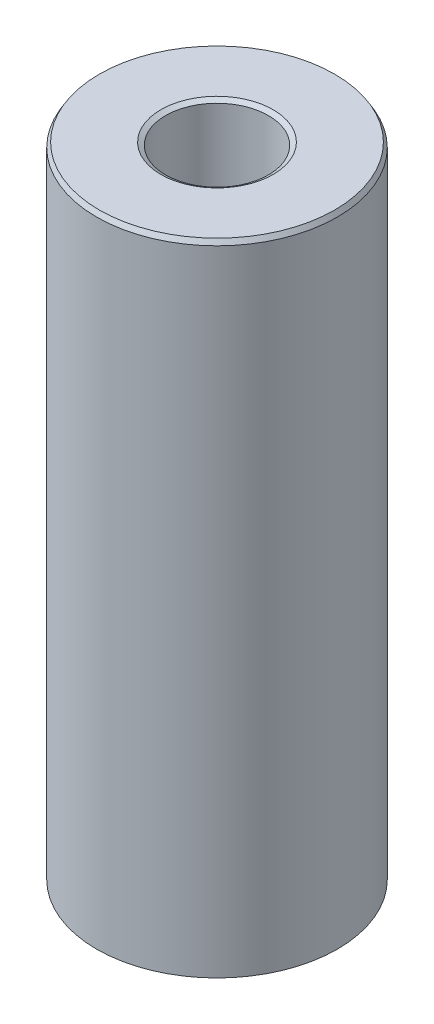
SolidWorks part; units mm, degrees
ref_plane "Front Plane" through (0, 0, 0) normal (0, 0, 1) x (1, 0, 0)
ref_plane "Top Plane" through (0, 0, 0) normal (0, 1, 0) x (1, 0, 0)
ref_plane "Right Plane" through (0, 0, 0) normal (1, 0, 0) x (0, 0, -1)
sketch "Sketch1" plane through (0, 0, 0) normal (0, 1, 0) x (1, 0, 0)
  circle A0 centre (0, 0) radius 37.5
  dimension "SLEEVE_OD" = 75
extrude "Boss-Extrude1" add sketch "Sketch1" along normal blind 199.793
sketch "Sketch2" plane through (0, 0, 0) normal (0, 1, 0) x (1, 0, 0)
  circle A0 centre (0, 0) radius 16.02
  dimension "BORE_D" = 32.0401
extrude "Cut-Extrude1" cut sketch "Sketch2" along normal through all
chamfer "Chamfer1" distance 1.4713 angle 30 4 edges at (0, 199.793, 16.02) (0, 0, 16.02) (0, 0, 37.5) (0, 199.793, 37.5) first distance on face at (0, 199.793, 16.02) first distance on face at (0, 0, 16.02) first distance on face at (0, 199.793, 37.5)
